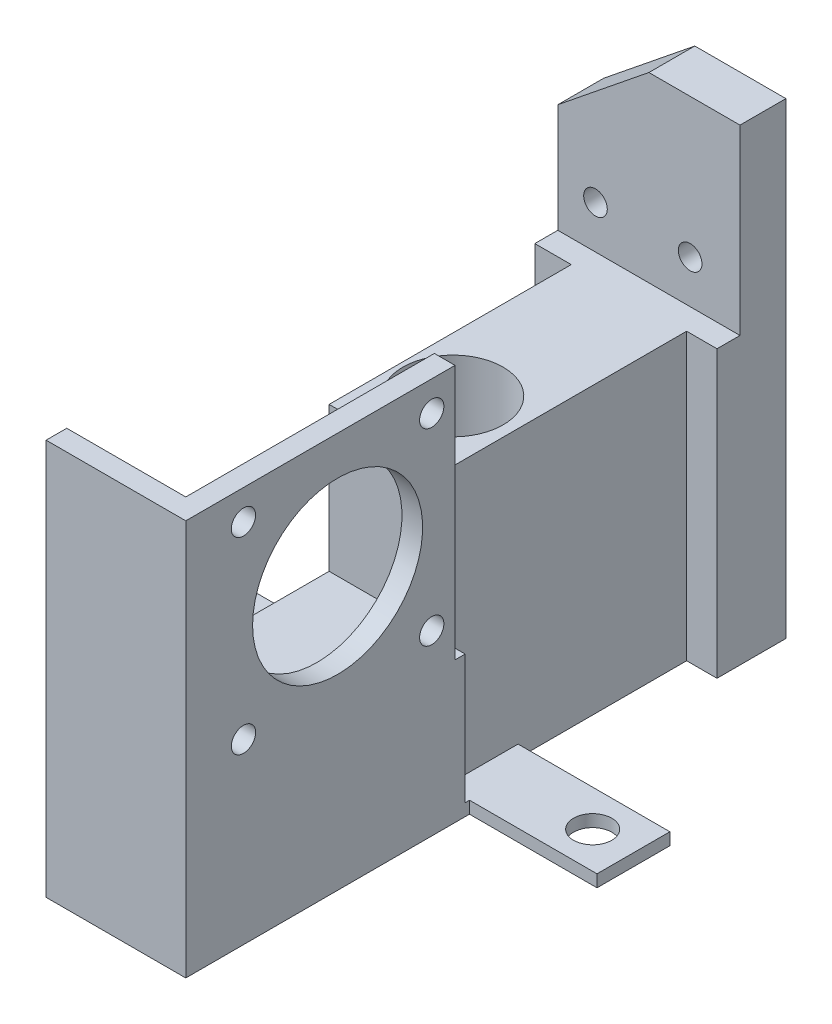
SolidWorks part; units mm, degrees
ref_plane "Front Plane" through (0, 0, 0) normal (0, 0, 1) x (1, 0, 0)
ref_plane "Top Plane" through (0, 0, 0) normal (0, 1, 0) x (1, 0, 0)
ref_plane "Right Plane" through (0, 0, 0) normal (1, 0, 0) x (0, 0, -1)
sketch "Sketch1" plane through (0, 0, 0) normal (0, 1, 0) x (1, 0, 0)
  line L0 (-48.7324, 38.4431) -> (21.2676, -31.5569) construction
  line L1 (-48.7324, 38.4431) -> (21.2676, 38.4431)
  line L2 (-48.7324, 38.4431) -> (-48.7324, -31.5569)
  line L4 (21.2676, 38.4431) -> (21.2676, -31.5569)
  line L5 (-48.7324, -31.5569) -> (21.2676, 38.4431) construction
  line L6 (-13.7324, 3.4431) -> (-13.7324, 29.4761) construction
  line L7 (-48.7324, -31.5569) -> (-48.7324, -79.8576)
  line L8 (-48.7324, -79.8576) -> (21.2676, -79.8576)
  line L9 (21.2676, -79.8576) -> (21.2676, -31.5569)
  circle A0 centre (-42.0166, 31.7274) radius 3.15
  circle A1 centre (14.5519, 31.7274) radius 3.15
  circle A2 centre (14.5519, -24.8412) radius 3.15
  circle A3 centre (-42.0166, -24.8412) radius 3.15
  circle A4 centre (-13.7324, -19.5569) radius 8.25
  point P6 (-13.7324, 3.4431)
  point P16 (-13.7324, 3.4431)
  dimension "D1" = 6.3
  dimension "D3" = 40
  dimension "D4" = 16.5
  dimension "D5" = 23
  dimension "D6" = 70
  dimension "D2" = 4
extrude "Boss-Extrude1" add sketch "Sketch1" along normal blind 2
sketch "Sketch2" plane through (0, 2, 0) normal (0, 1, 0) x (1, 0, 0)
  line L1 (-28.7324, 20.2631) -> (1.2676, 20.2631)
  line L2 (-28.7324, 20.2631) -> (-28.7324, 9.1031)
  line L5 (-13.7324, -36.2685) -> (-13.7324, 40.4624) construction
  line L6 (-48.7324, 38.4431) -> (-48.7324, -79.8576) construction
  line L7 (21.2676, -79.8576) -> (21.2676, 38.4431) construction
  line L10 (-22.7324, 12.2031) -> (-22.7324, -35.7969) construction
  line L11 (-22.7324, 5.9877) -> (-22.7324, -31.5569)
  line L12 (-22.7324, 8.8031) -> (-22.7324, -32.3969) construction
  line L15 (-22.7324, -31.5569) -> (-3.7324, -31.5569)
  line L34 (-22.7324, 8.9165) -> (-28.7324, 8.9165)
  line L41 (-28.7324, 8.9165) -> (-28.7324, 9.1031)
  line L42 (-22.7324, 8.9165) -> (-22.7324, 5.9877)
  line L43 (1.2676, 20.2631) -> (1.2676, 8.9165)
  line L44 (1.2676, 8.9165) -> (-3.7324, 8.9165)
  line L59 (-3.7324, 8.9165) -> (-3.7324, -31.5569)
  dimension "D1" = 30
extrude "Boss-Extrude2" add sketch "Sketch2" along normal blind 45
sketch "Sketch3" plane through (0, 2, 0) normal (0, -1, 0) x (1, 0, 0)
  circle A2 centre (-13.7324, 19.5569) radius 8.25
  circle A3 centre (-13.7324, 19.5569) radius 8.25
  dimension "D1" = 0
extrude "Cut-Extrude1" cut sketch "Sketch3" against normal through all
sketch "Sketch4" plane through (0, 47, 0) normal (0, 1, 0) x (1, 0, 0)
  line L0 (1.2676, 8.9165) -> (1.2676, 20.2631) construction
  line L3 (1.2676, 12.7031) -> (-28.7324, 12.7031)
  line L4 (1.2676, 12.7031) -> (1.2676, 20.2631)
  line L5 (1.2676, 20.2631) -> (-28.7324, 20.2631)
  line L6 (-28.7324, 12.7031) -> (-28.7324, 20.2631)
  line L8 (-25.7324, 12.2031) -> (-3.7324, 12.2031) construction
  dimension "D1" = 0.5
extrude "Boss-Extrude3" add sketch "Sketch4" along normal blind 30
sketch "Sketch5" plane through (0, 0, -12.7031) normal (0, 0, 1) x (1, 0, 0)
  circle A0 centre (-22.5274, 54.0695) radius 1.945
  circle A1 centre (-6.9374, 54.0695) radius 1.945
extrude "Cut-Extrude2" cut sketch "Sketch5" against normal through all
sketch "Sketch6" plane through (0, 2, 0) normal (0, 1, 0) x (1, 0, 0)
  line L0 (-48.7324, 38.4431) -> (-48.7324, -79.8576) construction
  line L10 (-22.7324, 8.9165) -> (-22.7324, -31.5569) construction
  line L28 (-48.7324, -18.8412) -> (-22.7324, -18.8412)
  line L29 (-3.7324, -18.8412) -> (21.2676, -18.8412)
  line L30 (-3.7324, -31.5569) -> (-3.7324, 8.9165) construction
  line L31 (21.2676, -79.8576) -> (21.2676, 38.4431) construction
  line L79 (-22.7324, 8.9165) -> (-22.7324, -31.5569)
  line L80 (-22.7324, 8.9165) -> (-22.7324, -18.8412)
  line L82 (-28.7324, 8.9165) -> (-22.7324, 8.9165)
  line L83 (-28.7324, 8.9165) -> (-22.7324, 8.9165)
  line L85 (-28.7324, 12.7031) -> (-28.7324, 8.9165)
  line L86 (-28.7324, 12.7031) -> (-28.7324, 8.9165)
  line L95 (1.2676, 12.7031) -> (1.2676, 20.2631)
  line L96 (1.2676, 20.2631) -> (-28.7324, 20.2631)
  line L97 (-28.7324, 20.2631) -> (-28.7324, 12.7031)
  line L98 (1.2676, 8.9165) -> (1.2676, 20.2631)
  line L99 (1.2676, 20.2631) -> (-28.7324, 20.2631)
  line L100 (-28.7324, 20.2631) -> (-28.7324, 12.7031)
  line L101 (1.2676, 8.9165) -> (1.2676, 20.2631)
  line L105 (-3.7324, -31.5569) -> (-3.7324, 8.9165)
  line L106 (-3.7324, 8.9165) -> (1.2676, 8.9165)
  line L107 (-3.7324, -18.8412) -> (-3.7324, 8.9165)
  line L108 (-3.7324, 8.9165) -> (1.2676, 8.9165)
  line L110 (-48.7324, -30.8412) -> (-44.9403, -30.8412)
  line L111 (0.2676, -30.8412) -> (21.2676, -30.8412)
  line L113 (21.2676, -79.8576) -> (21.2676, 38.4431)
  line L114 (21.2676, 38.4431) -> (-48.7324, 38.4431)
  line L115 (-48.7324, 38.4431) -> (-48.7324, -79.8576)
  line L116 (21.2676, -18.8412) -> (21.2676, 38.4431)
  line L117 (21.2676, 38.4431) -> (-48.7324, 38.4431)
  line L118 (-48.7324, 38.4431) -> (-48.7324, -18.8412)
  line L119 (-44.9403, -30.8412) -> (-44.9403, -77.5569)
  line L120 (-44.9403, -77.5569) -> (0.2676, -77.5569)
  line L121 (0.2676, -77.5569) -> (0.2676, -30.8412)
  line L122 (-48.7324, -30.8412) -> (-48.7324, -79.8576)
  line L123 (-48.7324, -79.8576) -> (21.2676, -79.8576)
  line L124 (21.2676, -79.8576) -> (21.2676, -30.8412)
  line L125 (-4.2324, -73.5569) -> (-42.7324, -73.5569) construction
  line L126 (-3.7324, -36.7995) -> (-3.7324, -68.3143) construction
  circle A0 centre (-42.0166, -24.8412) radius 3.15 construction
  dimension "D1" = 6
  dimension "D9" = 6
  dimension "D10" = 4
  dimension "D11" = 4
  dimension "D2" = 0
  dimension "D3" = 0
  dimension "D4" = 0
  dimension "D5" = 0
  dimension "D6" = 0
  dimension "D7" = 0
  dimension "D8" = 0
extrude "Cut-Extrude3" cut sketch "Sketch6" against normal through all
sketch "Sketch10" plane through (0, 2, 0) normal (0, 1, 0) x (1, 0, 0)
  line L0 (0.2676, -77.5569) -> (-44.9403, -77.5569) construction
  line L1 (0.2676, -77.5569) -> (-22.7324, -77.5569)
  line L2 (0.2676, -77.5569) -> (0.2676, -31.5569)
  line L3 (0.2676, -31.5569) -> (-22.7324, -31.5569)
  line L4 (-22.7324, -77.5569) -> (-22.7324, -31.5569)
  line L5 (0.2676, -30.8412) -> (0.2676, -77.5569) construction
extrude "Boss-Extrude4" add sketch "Sketch10" along normal blind 21.2
sketch "Sketch11" plane through (0, 2, 0) normal (0, 1, 0) x (1, 0, 0)
  line L1 (-44.9403, -30.8412) -> (-22.7324, -30.8412)
  line L2 (-44.9403, -30.8412) -> (-44.9403, -77.5569)
  line L3 (-44.9403, -77.5569) -> (-22.7324, -77.5569)
  line L4 (-22.7324, -30.8412) -> (-22.7324, -77.5569)
extrude "Cut-Extrude4" cut sketch "Sketch11" against normal through all
sketch "Sketch12" plane through (-22.7324, 0, 0) normal (-1, 0, 0) x (0, 0, 1)
  line L0 (-8.9165, 47) -> (31.5569, 47) construction
  line L1 (31.5569, 23.2) -> (30.9569, 23.2)
  line L2 (31.5569, 23.2) -> (31.5569, 47)
  line L3 (31.5569, 47) -> (30.9569, 47)
  line L4 (30.9569, 23.2) -> (30.9569, 47)
  dimension "D1" = 0.6
extrude "Cut-Extrude5" cut sketch "Sketch12" against normal through all
sketch "Sketch13" plane through (0, 23.2, 0) normal (0, 1, 0) x (1, 0, 0)
  line L0 (-22.7324, -30.9569) -> (-22.7324, -77.5569) construction
  line L1 (0.2676, -77.5569) -> (-22.7324, -77.5569)
  line L2 (0.2676, -77.5569) -> (0.2676, -74.1569)
  line L3 (-3.1324, -74.1569) -> (-22.7324, -74.1569)
  line L4 (-22.7324, -77.5569) -> (-22.7324, -74.1569)
  line L5 (-4.2324, -73.5569) -> (-42.7324, -73.5569) construction
  line L7 (0.2676, -74.1569) -> (0.2676, -33.2235)
  line L8 (0.2676, -33.2235) -> (-3.1324, -33.2235)
  line L9 (-3.1324, -74.1569) -> (-3.1324, -33.2235)
  line L10 (-3.7324, -36.7995) -> (-3.7324, -68.3143) construction
  dimension "D1" = 0.6
  dimension "D2" = 0.6
extrude "Boss-Extrude5" add sketch "Sketch13" along normal blind 42
sketch "Sketch14" plane through (-3.1324, 0, 0) normal (-1, 0, 0) x (0, 0, 1)
  circle A0 centre (52.5569, 44.7853) radius 14
  dimension "D1" = 28
extrude "Cut-Extrude6" cut sketch "Sketch14" against normal through all
sketch "Sketch15" plane through (-3.1324, 0, 0) normal (-1, 0, 0) x (0, 0, 1)
  circle A0 centre (68.0569, 29.2853) radius 2
  circle A1 centre (37.0569, 29.2853) radius 2
  circle A2 centre (37.0569, 60.2853) radius 2
  circle A4 centre (68.0569, 60.2853) radius 2
  dimension "D1" = 4
extrude "Cut-Extrude7" cut sketch "Sketch15" against normal through all
sketch "Sketch16" plane through (0, 0, -20.2631) normal (0, 0, -1) x (-1, 0, 0)
  line L0 (28.7324, 64.9066) -> (13.7324, 77)
  line L1 (28.7324, 77) -> (28.7324, 0) construction
  line L2 (42.7324, 64.9066) -> (4.2324, 64.9066) construction
  line L3 (-1.2676, 77) -> (28.7324, 77) construction
  line L4 (13.7324, 77) -> (28.7324, 77)
  line L5 (28.7324, 77) -> (28.7324, 64.9066)
extrude "Cut-Extrude8" cut sketch "Sketch16" against normal through all
